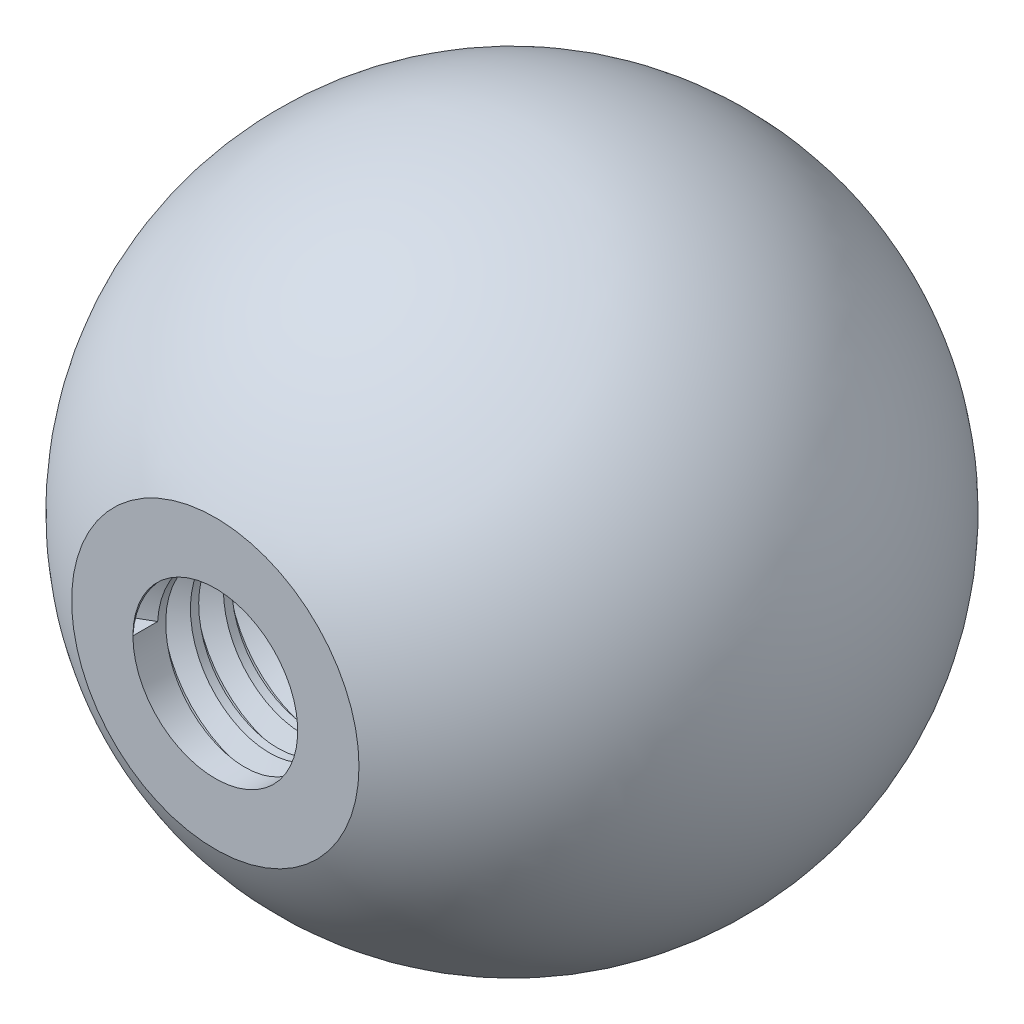
SolidWorks part; units mm, degrees
material "Rubber"
ref_plane "Front Plane" through (0, 0, 0) normal (0, 0, 1) x (1, 0, 0)
ref_plane "Top Plane" through (0, 0, 0) normal (0, 1, 0) x (1, 0, 0)
ref_plane "Right Plane" through (0, 0, 0) normal (1, 0, 0) x (0, 0, -1)
sketch "Sketch1" plane through (0, 0, 0) normal (0, 0, 1) x (1, 0, 0)
  line L0 (0, 0) -> (-12.7, 0)
  line L1 (0, 0) -> (12.7, 0)
  arc A0 (12.7, 0) -> (-12.7, 0) centre (0, 0) ccw
revolve "Revolve1" add sketch "Sketch1" angle 360 about L0
ref_plane "Plane1" through (0, 0, 12.7) normal (0, 0, 1) x (1, 0, 0)
sketch "Sketch2" plane through (0, 0, 12.7) normal (0, 0, 1) x (1, 0, 0)
  circle A0 centre (0, 0) radius 12.7
extrude "Cut-Extrude1" cut sketch "Sketch2" against normal blind 1.27
sketch "Sketch3" plane through (0, 0, 11.43) normal (0, 0, 1) x (1, 0, 0)
  circle A0 centre (0, 0) radius 3.175
hole_wizard "1/4 (0.25) Diameter Hole1" positions "Sketch4" profile "Sketch5" hole size "1/4" standard "ANSI Inch"
sketch "Sketch4" plane through (0, 0, 11.43) normal (0, 0, 1) x (1, 0, 0)
  point P0 (0, 0)
sketch "Sketch5" plane through (0, 0, 11.43) normal (1, 0, 0) x (0, -1, 0)
  line L0 (0, 0) -> (0, 12.0677)
  line L1 (0, 12.0677) -> (3.175, 10.16)
  line L2 (3.175, 10.16) -> (3.175, 0)
  line L5 (3.175, 0) -> (0, 0)
  line L10 (0, 12.0677) -> (-3.175, 10.16) construction
  line L11 (0, -6.35) -> (0, 107.95) construction
  dimension "Hole Dia." = 6.35
  dimension "Hole Depth" = 10.16
  dimension "Drill Angle" = 118
thread "Thread2" pitch 1.27 method cut profile "Thread Profile2" start angle 0, offset 0, length 0, pitch 1.27, diameter 6.35
ref_plane "Plane3" through (-3.175, 0, 11.43) normal (0, -1, 0) x (-1, 0, 0)
sketch "Thread Profile2" plane through (-3.175, 0, 11.43) normal (0, -1, 0) x (-1, 0, 0)
  line L0 (0, 0) -> (0, 1.27) construction
  line L1 (0, 0) -> (0.6874, 0.3969)
  line L2 (0.6874, 0.3969) -> (0.6874, 0.5556)
  line L3 (0.6874, 0.5556) -> (0, 0.9525)
  line L4 (0.6874, 0.4762) -> (0, 0.4762) construction
  line L11 (0, 0) -> (0, 0.9525)
  point P2 (0, 0)
  dimension "Pitch" = 1.27
  dimension "Profile_Angle" = 60
  dimension "Profile_Land" = 0.1588
  dimension "Profile_Height" = 0.6874
